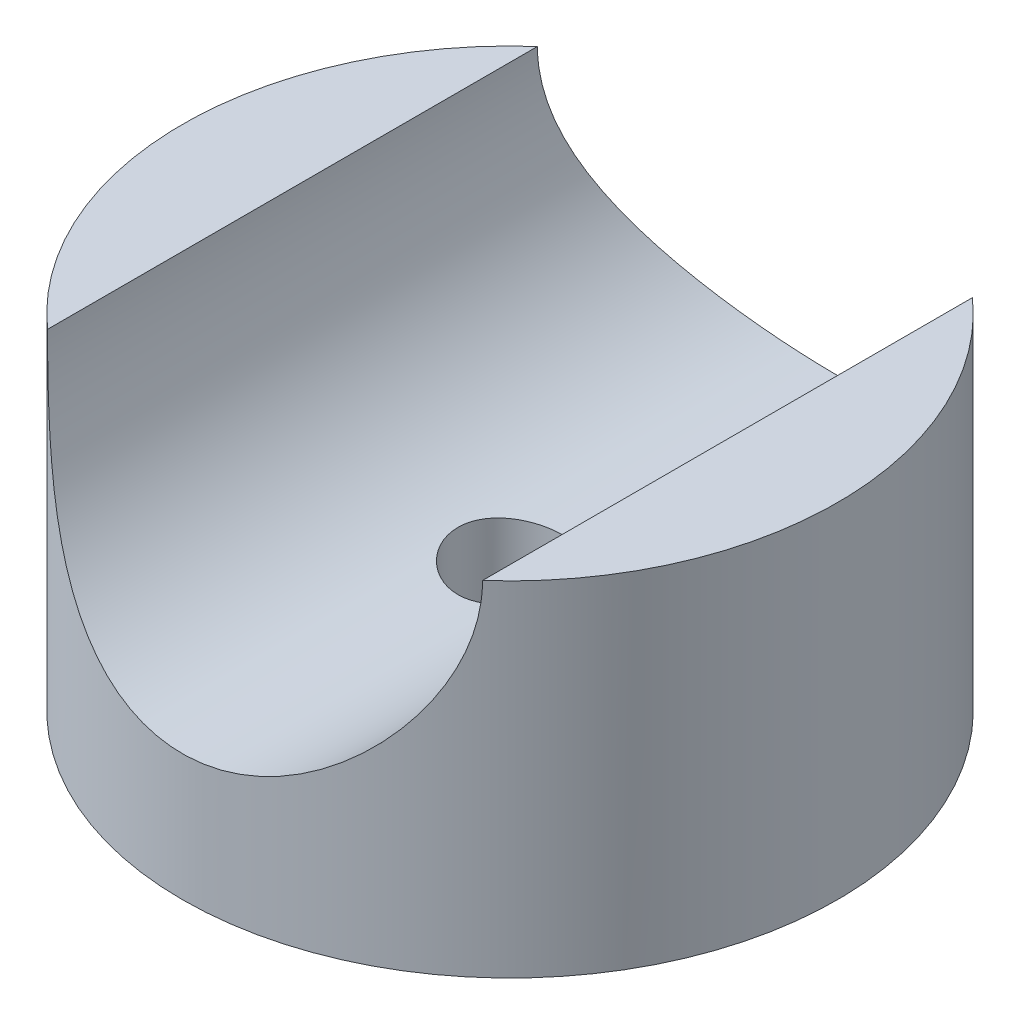
SolidWorks part; units mm, degrees
ref_plane "Front Plane" through (0, 0, 0) normal (0, 0, 1) x (1, 0, 0)
ref_plane "Top Plane" through (0, 0, 0) normal (0, 1, 0) x (1, 0, 0)
ref_plane "Right Plane" through (0, 0, 0) normal (1, 0, 0) x (0, 0, -1)
sketch "Sketch1" plane through (0, 0, 0) normal (0, 1, 0) x (1, 0, 0)
  circle A0 centre (0, 0) radius 31.75
  dimension "D1" = 63.5
extrude "Boss-Extrude1" add sketch "Sketch1" along normal blind 33.3375
hole_wizard "3/8 Clearance Hole1" positions "Sketch2" profile "Sketch3" hole size "3/8" standard "ANSI Inch" end condition through all
sketch "Sketch2" plane through (0, 33.3375, 0) normal (0, 1, 0) x (1, 0, 0)
  point P0 (0, 0)
sketch "Sketch3" plane through (0, 33.3375, 0) normal (1, 0, 0) x (0, 0, 1)
  line L0 (0, 0) -> (0, 33.3375)
  line L1 (0, 33.3375) -> (5.0419, 33.3375)
  line L2 (5.0419, 33.3375) -> (5.0419, 0)
  line L5 (5.0419, 0) -> (0, 0)
  line L11 (0, -6.35) -> (0, 107.95) construction
  dimension "Thru Hole Dia." = 10.0838
  dimension "Thru Hole Depth" = 33.3375
sketch "Sketch4" plane through (0, 0, 0) normal (0, 0, 1) x (1, 0, 0)
  line L0 (5.0419, 33.3375) -> (-5.0419, 33.3375) construction
  circle A0 centre (0, 33.3375) radius 21.082
  dimension "D1" = 42.164
extrude "Cut-Extrude1" cut sketch "Sketch4" against normal blind 50.8 and the other way blind 50.8
hole_wizard "Tap Drill for #10-24 Tap1" positions "Sketch5" profile "Sketch6" hole size "#10-24" standard "ANSI Inch"
sketch "Sketch5" plane through (0, 0, 0) normal (0, -1, 0) x (-1, 0, 0)
  line L0 (0, 31.75) -> (0, -31.75) construction
  line L2 (31.75, 0) -> (-31.75, 0) construction
  circle A0 centre (0, 0) radius 31.75 construction
  point P0 (25.4, -9.525)
  point P2 (25.4, 9.525)
  point P4 (-25.4, 9.525)
  point P6 (-25.4, -9.525)
  point P19 (25.0121, 5.8394)
  point P20 (24.3442, 5.8394)
  point P21 (0, 0)
  point P22 (24.1432, 6.2218)
  point P23 (0, 0)
  point P24 (0, 0)
  point P25 (0, 0)
  point P26 (0, 0)
  point P27 (0, 0)
  dimension "D1" = 50.8
  dimension "D2" = 19.05
sketch "Sketch6" plane through (-25.4, 0, 9.525) normal (1, 0, 0) x (0, 0, -1)
  line L0 (0, 0) -> (0, 20.1908)
  line L1 (0, 20.1908) -> (1.8986, 19.05)
  line L2 (1.8986, 19.05) -> (1.8986, 0)
  line L5 (1.8986, 0) -> (0, 0)
  line L10 (0, 20.1908) -> (-1.8987, 19.05) construction
  line L11 (0, -6.35) -> (0, 107.95) construction
  dimension "Hole Dia." = 3.7973
  dimension "Hole Depth" = 19.05
  dimension "Drill Angle" = 118
